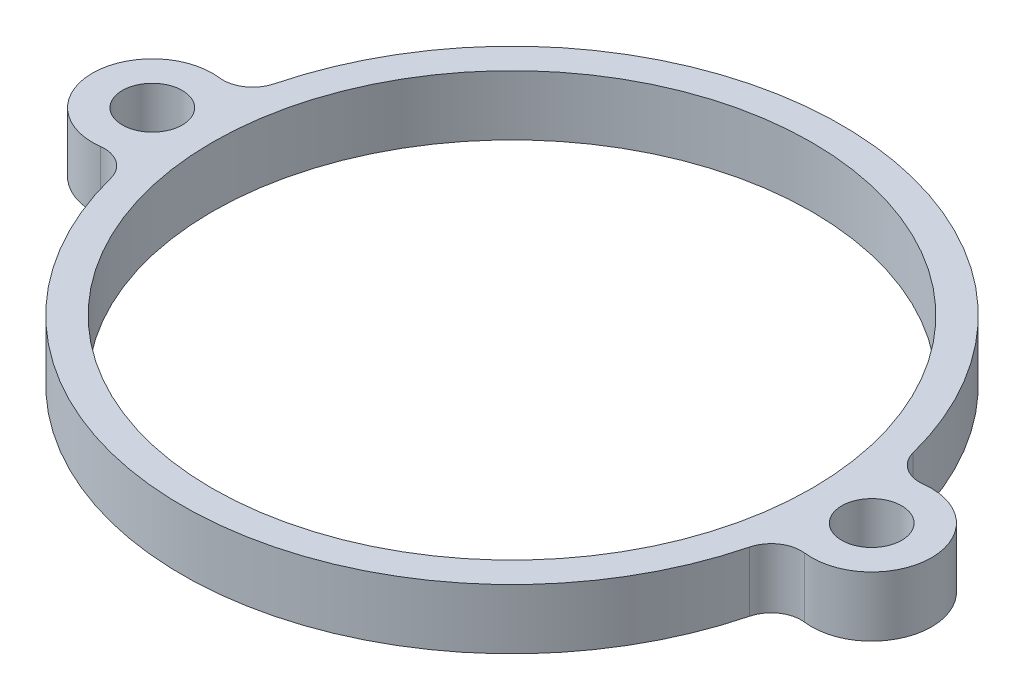
SolidWorks part; units mm, degrees
ref_plane "Front Plane" through (0, 0, 0) normal (0, 0, 1) x (1, 0, 0)
ref_plane "Top Plane" through (0, 0, 0) normal (0, 1, 0) x (1, 0, 0)
ref_plane "Right Plane" through (0, 0, 0) normal (1, 0, 0) x (0, 0, -1)
sketch "Sketch1" plane through (0, 0, 0) normal (0, 1, 0) x (1, 0, 0)
  line L0 (0, 0) -> (60, 0) construction
  line L1 (0, 0) -> (-60, 0) construction
  circle A0 centre (0, 0) radius 50
  circle A1 centre (-60, 0) radius 5
  circle A2 centre (60, 0) radius 5
  arc A3 (-53.2813, -13.6422) -> (53.2812, -13.6422) centre (0, 0) ccw
  arc A4 (-58.75, 9.9216) -> (-58.75, -9.9216) centre (-60, 0) ccw
  arc A5 (58.75, -9.9216) -> (58.75, 9.9216) centre (60, 0) ccw
  arc A6 (53.2813, 13.6422) -> (-53.2813, 13.6422) centre (0, 0) ccw
  circle A7 centre (-60, 0) radius 10 construction
  circle A8 centre (0, 0) radius 55 construction
  circle A9 centre (60, 0) radius 10 construction
  arc A10 (58.75, -9.9216) -> (53.2812, -13.6422) centre (58.125, -14.8824) ccw
  arc A11 (58.75, 9.9216) -> (53.2813, 13.6422) centre (58.125, 14.8824) cw
  arc A12 (-58.75, 9.9216) -> (-53.2813, 13.6422) centre (-58.125, 14.8824) ccw
  arc A13 (-58.75, -9.9216) -> (-53.2813, -13.6422) centre (-58.125, -14.8824) cw
  point P8 (70, 0)
  point P13 (-50, 0)
  point P15 (55, 0)
  point P24 (54.375, 8.268)
  dimension "D1" = 100
  dimension "D3" = 10
  dimension "D5" = 5
  dimension "D2" = 60
  dimension "D4" = 5
extrude "Boss-Extrude1" add sketch "Sketch1" along normal blind 10
